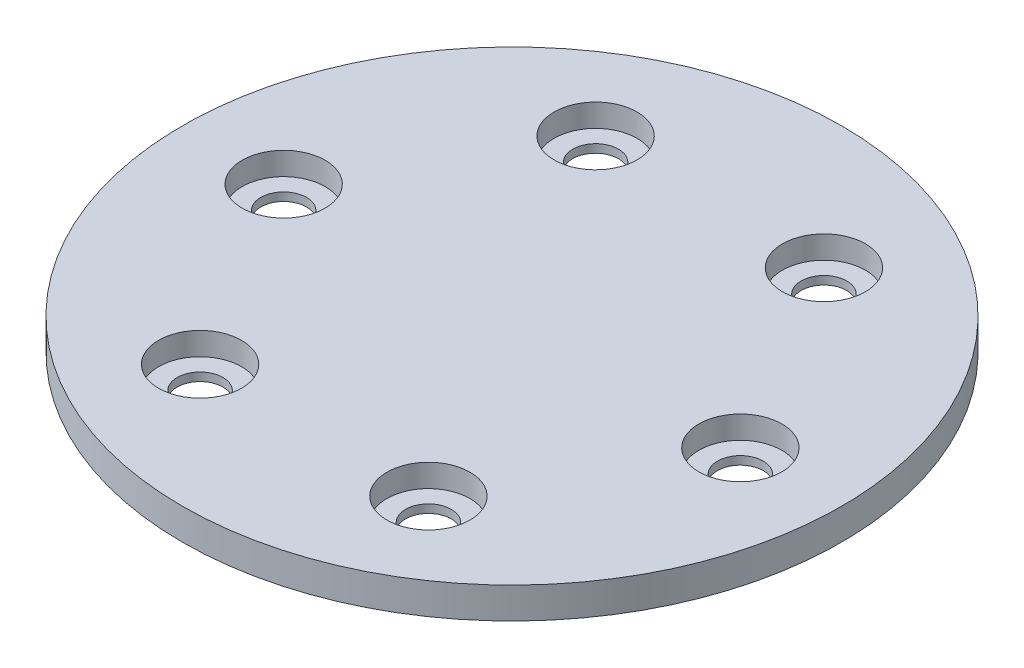
SolidWorks part; units mm, degrees
material "1060 Alloy"
ref_plane "Front Plane" through (0, 0, 0) normal (0, 0, 1) x (1, 0, 0)
ref_plane "Top Plane" through (0, 0, 0) normal (0, 1, 0) x (1, 0, 0)
ref_plane "Right Plane" through (0, 0, 0) normal (1, 0, 0) x (0, 0, -1)
sketch "Sketch1" plane through (0, 0, 0) normal (0, 1, 0) x (1, 0, 0)
  circle A0 centre (0, 0) radius 15.875
  dimension "D1" = 31.75
extrude "Boss-Extrude1" add sketch "Sketch1" along normal blind 1.5
sketch "Sketch3" plane through (0, 1.5, 0) normal (0, 1, 0) x (1, 0, 0)
  circle A0 centre (0, -10.25) radius 0.25
  circle A1 centre (0, 0) radius 9.8
  dimension "D1" = 0.5
  dimension "D2" = 10.25
  dimension "D3" = 19.6
sketch "Sketch4" plane through (0, 1.5, 0) normal (0, -1, 0) x (1, 0, 0)
  line L0 (0, 0) -> (13.2597, 13.2597) construction
  circle A0 centre (7.7782, 7.7782) radius 1
  dimension "D2" = 2
  dimension "D1" = 11
sketch "Sketch5" plane through (0, 1.5, 0) normal (0, 1, 0) x (1, 0, 0)
  circle A0 centre (0, 0) radius 11
  dimension "D1" = 22
hole_wizard "CBORE for M5 Hex Head Bolt1" positions "Sketch6" profile "Sketch7" counterbore size "M5" standard "ISO"
sketch "Sketch6" plane through (0, 1.5, 0) normal (0, 1, 0) x (1, 0, 0)
  point P0 (11, 0)
  dimension "D1" = 11
sketch "Sketch7" plane through (11, 1.5, 0) normal (1, 0, 0) x (0, 0, 1)
  line L0 (0, 0) -> (0, 5.6609)
  line L1 (0, 5.6609) -> (1.1, 5)
  line L2 (1.1, 5) -> (1.1, 1.1)
  line L3 (1.1, 1.1) -> (2, 1.1)
  line L4 (2, 1.1) -> (2, 0)
  line L5 (2, 0) -> (0, 0)
  line L10 (0, 5.6609) -> (-1.1, 5) construction
  line L11 (0, -6.35) -> (0, 107.95) construction
  dimension "Hole Dia." = 2.2
  dimension "Hole Depth" = 5
  dimension "C'Bore Dia." = 4
  dimension "C'Bore Depth" = 1.1
  dimension "Drill Angle" = 118
pattern_circular "CirPattern1" count 6 over 360 about axis through (0, 1.5, 0) along (0, 1, 0) of "CBORE for M5 Hex Head Bolt1"
